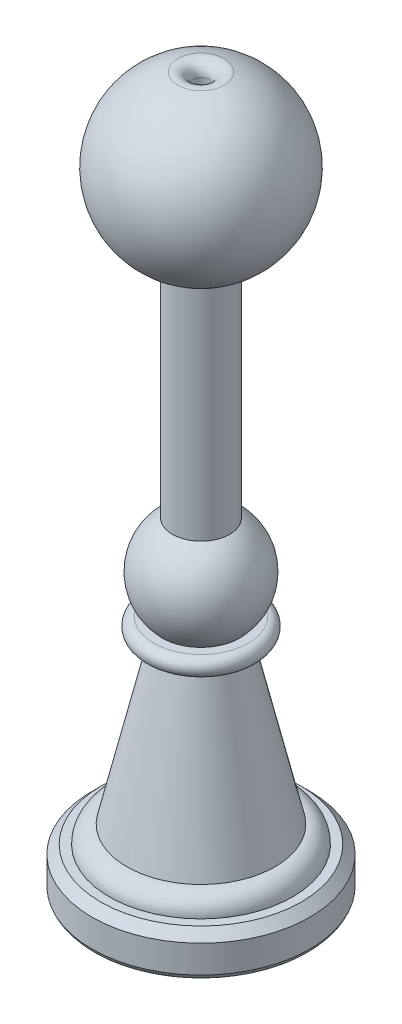
SolidWorks part; units mm, degrees
ref_plane "Front Plane" through (0, 0, 0) normal (0, 0, 1) x (1, 0, 0)
ref_plane "Top Plane" through (0, 0, 0) normal (0, 1, 0) x (1, 0, 0)
ref_plane "Right Plane" through (0, 0, 0) normal (1, 0, 0) x (0, 0, -1)
sketch "Sketch1" plane through (0, 0, 0) normal (0, 0, 1) x (1, 0, 0)
  line L0 (0, 0) -> (0, 28.575) construction
  line L1 (0, 0) -> (-9.525, 0)
  line L2 (-9.525, 0) -> (-9.525, 3.175)
  line L3 (-9.525, 3.175) -> (-8.001, 3.175)
  line L4 (-8.001, 3.175) -> (-8.001, 4.699)
  line L5 (-8.001, 4.699) -> (-6.477, 4.699)
  line L6 (-6.477, 4.699) -> (-3.175, 18.923)
  line L7 (-3.175, 18.923) -> (-4.1317, 18.923)
  line L9 (-4.1317, 20.447) -> (-3.3697, 20.447)
  line L10 (0, 28.575) -> (0, 0)
  arc A0 (0, 28.575) -> (-3.3697, 20.447) centre (0, 23.8125) ccw
  arc A1 (-4.1317, 18.923) -> (-4.1317, 20.447) centre (-4.1317, 19.685) cw
  dimension "D2" = 3.175
  dimension "D10" = 9.525
  dimension "D9" = 1.524
  dimension "D1" = 28.575
  dimension "D3" = 3.175
  dimension "D4" = 1.524
  dimension "D5" = 1.524
  dimension "D6" = 9.525
  dimension "D7" = 1.524
  dimension "D8" = 1.524
  dimension "D11" = 14.224
revolve "Revolve1" add sketch "Sketch1" angle 360 about L0
fillet "Fillet1" radius 1.524 1 edges at (0, 4.699, -8.001)
chamfer "Chamfer1" distance 0.762 angle 45 1 edges at (0, 3.175, -9.525)
sketch "Sketch2" plane through (0, 3.175, 0) normal (0, 1, 0) x (1, 0, 0)
  point P0 (0, 0)
sketch "Sketch3" plane through (0, 0, 0) normal (0, -1, 0) x (1, 0, 0)
  circle A0 centre (0, 0) radius 9.525 construction
  point P0 (0, 0)
  point P1 (9.525, 0)
ref_plane "Plane1" through (0, 0, 0) normal (0, 0, 1) x (1, 0, 0)
sketch "Sketch4" plane through (0, 0, 0) normal (0, 0, 1) x (1, 0, 0)
  line L0 (0, 0) -> (-10, 0)
  line L1 (-10, 0) -> (-5.37, -2.68)
  line L2 (-5.37, -2.68) -> (0, -2.68)
  line L3 (0, -2.68) -> (0, 0)
  line L4 (0, 28.575) -> (0, 73.4076) construction
  line L6 (0, 27.0664) -> (-2.5, 27.0664)
  line L7 (0, 27.0664) -> (0, 47.32)
  line L8 (0, 47.32) -> (-2.5, 47.32)
  line L9 (-2.5, 27.0664) -> (-2.5, 47.32)
  arc A0 (3.3697, 20.447) -> (-3.3697, 20.447) centre (0, 23.8125) ccw construction
  circle A1 centre (0, 54.3911) radius 7.5
  dimension "D7" = 15
  dimension "D1" = 10
  dimension "D2" = 2.68
  dimension "D3" = 5.37
  dimension "D4" = 2.5
  dimension "D5" = 2.5
  dimension "D6" = 50
revolve "Revolve2" add sketch "Sketch4" angle 360 about L4 region at (-3.9587, -1.2054, 0) region at (-1.2544, 37.0498, 0) region at (-0.9412, 47.148, 0) region at (-3.2015, 54.4505, 0)
sketch "Sketch5" plane through (0, -2.68, 0) normal (0, -1, 0) x (1, 0, 0)
  circle A0 centre (0, 0) radius 0.75
  dimension "D1" = 1.5
extrude "Cut-Extrude1" cut sketch "Sketch5" against normal blind 65
fillet "Fillet2" radius 1 2 edges at (10, 0, 0) (0.75, 61.8535, 0)
sketch "Sketch6" plane through (0, -2.68, 0) normal (0, -1, 0) x (1, 0, 0)
  circle A0 centre (0, 0) radius 5.1
  dimension "D1" = 10.2
extrude "Cut-Extrude2" cut sketch "Sketch6" against normal blind 4
fillet "Fillet3" radius 1 1 edges at (5.1, -2.68, 0)
